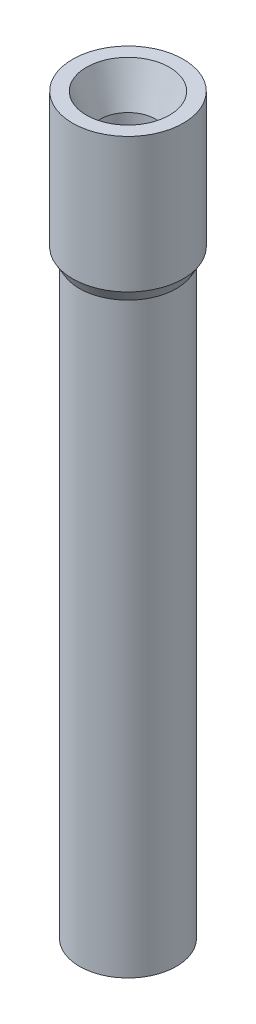
SolidWorks part; units mm, degrees
ref_plane "前视基准面" through (0, 0, 0) normal (0, 0, 1) x (1, 0, 0)
ref_plane "上视基准面" through (0, 0, 0) normal (0, 1, 0) x (1, 0, 0)
ref_plane "右视基准面" through (0, 0, 0) normal (1, 0, 0) x (0, 0, -1)
other "Configuration Table"
sketch "草图1" plane through (0, 0, 0) normal (0, 1, 0) x (1, 0, 0)
  circle A0 centre (0, 0) radius 4
  circle A1 centre (0, 0) radius 3.5
extrude "凸台-拉伸1" add sketch "草图1" along normal blind 8 contours A0
sketch "草图2" plane through (0, 0, 0) normal (0, -1, 0) x (1, 0, 0)
  circle A0 centre (0, 0) radius 3.5
extrude "凸台-拉伸2" add sketch "草图2" along normal blind 45
chamfer "倒角1" distance 1.5 angle 60 1 edges at (0, 0, -3.5) first distance on face at (0, 0, -3.5)
sketch "草图3" plane through (0, -45, 0) normal (0, -1, 0) x (1, 0, 0)
  circle A0 centre (0, 0) radius 2
extrude "切除-拉伸1" cut sketch "草图3" against normal blind 101
chamfer "倒角2" distance 1 angle 70 1 edges at (0, 8, 2) first distance on face at (0, 8, 2)
